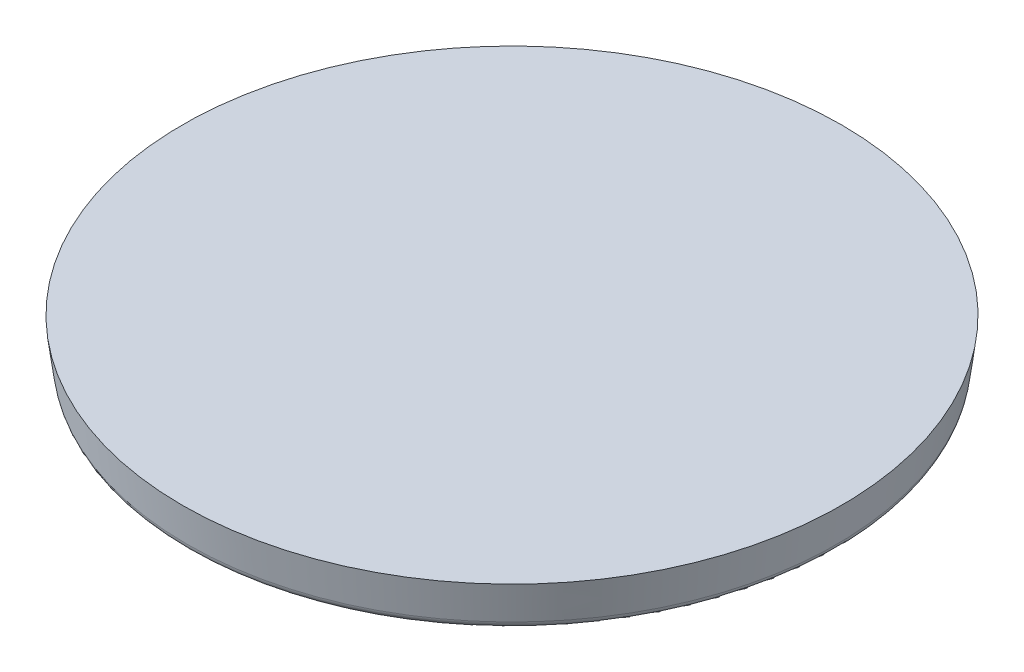
SolidWorks part; units mm, degrees
material "6061-T6 (SS)"
ref_plane "Front Plane" through (0, 0, 0) normal (0, 0, 1) x (1, 0, 0)
ref_plane "Top Plane" through (0, 0, 0) normal (0, 1, 0) x (1, 0, 0)
ref_plane "Right Plane" through (0, 0, 0) normal (1, 0, 0) x (0, 0, -1)
sketch "Sketch2" plane through (0, 0, 0) normal (0, 0, 1) x (1, 0, 0)
  line L0 (0, 0) -> (14.097, 0)
  line L1 (14.097, 0) -> (14.3478, 1.905)
  line L2 (14.3478, 1.905) -> (0, 1.905)
  line L4 (0, 1.905) -> (0, 0) construction
  line L5 (0, 1.905) -> (0, 0)
  dimension "D1" = 1.905
  dimension "D2" = 28.194
  dimension "D3" = 7.5
revolve "Revolve1" add sketch "Sketch2" angle 360 about L4
sketch "Sketch3" plane through (0, 0, 0) normal (0, -1, 0) x (1, 0, 0)
  line L0 (0, -0.7937) -> (0, 0.7937) construction
  line L1 (-3.0742, 0.7937) -> (3.0742, 0.7937)
  line L3 (-3.0742, -0.7937) -> (3.0742, -0.7937)
  arc A0 (-3.0742, -0.7937) -> (3.0742, -0.7937) centre (0, 0) ccw
  arc A1 (3.0742, 0.7937) -> (-3.0742, 0.7937) centre (0, 0) ccw
  point P10 (0, 0)
  dimension "D1" = 6.35
  dimension "D2" = 1.5875
extrude "Boss-Extrude1" add sketch "Sketch3" along normal blind 2.54
fillet "Fillet1" radius 2.54 2 edges at (0, 0, -3.175) (0, 0, 3.175)
fillet "Match Tool Radius" radius 0.381 1 edges at (0, 0, 14.097)
